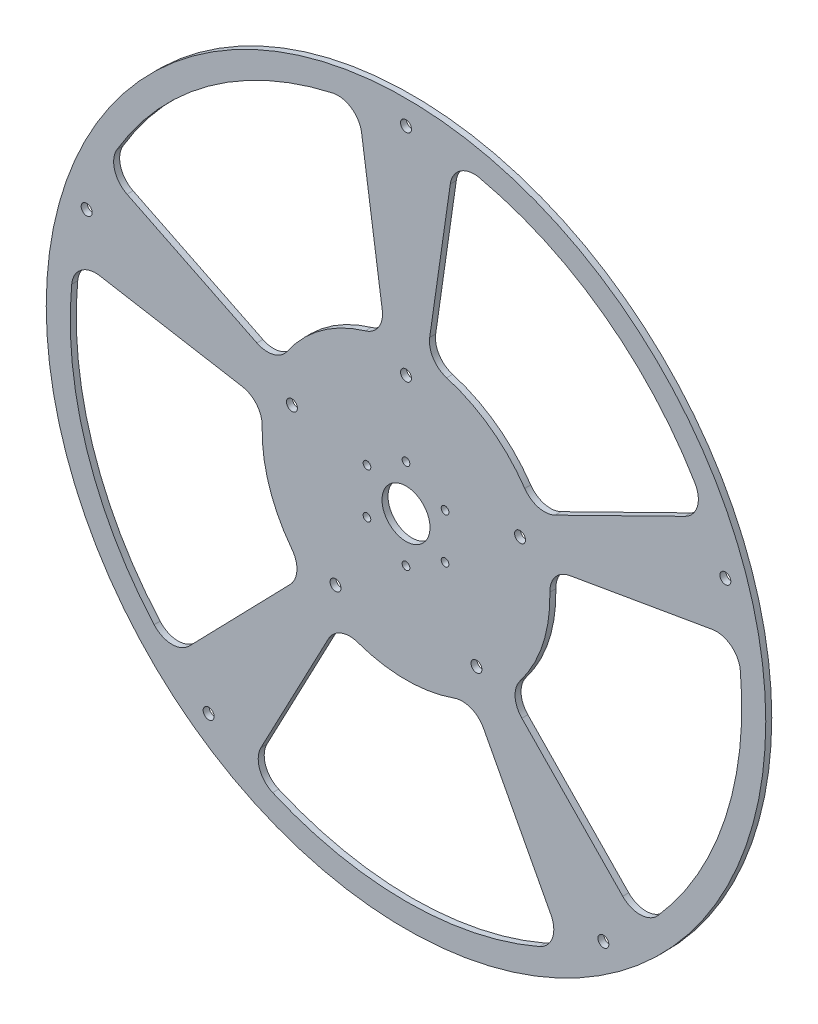
SolidWorks part; units mm, degrees
material "6061 Alloy"
ref_plane "Front Plane" through (0, 0, 0) normal (0, 0, 1) x (1, 0, 0)
ref_plane "Top Plane" through (0, 0, 0) normal (0, 1, 0) x (1, 0, 0)
ref_plane "Right Plane" through (0, 0, 0) normal (1, 0, 0) x (0, 0, -1)
sketch "Sketch1" plane through (0, 0, 0) normal (0, 0, 1) x (1, 0, 0)
  line L0 (0, 177.8) -> (0, 0) construction
  line L1 (0, 0) -> (169.0978, 54.9432) construction
  line L2 (-169.0978, 54.9432) -> (0, 0) construction
  line L3 (0, 0) -> (-104.5082, -143.8432) construction
  line L4 (0, 0) -> (104.5082, -143.8432) construction
  line L5 (25.3351, 175.9857) -> (10.8579, 75.4224)
  line L6 (-25.4, 175.9764) -> (-10.8857, 75.4184)
  line L7 (68.3757, 33.6333) -> (159.5434, 78.4777)
  line L8 (75.0863, 12.9803) -> (175.2013, 30.2874)
  line L9 (53.1164, -54.6359) -> (123.9384, -127.4838)
  line L10 (35.548, -67.4002) -> (82.9453, -157.267)
  line L11 (-159.5434, 78.4777) -> (-68.3757, 33.6333)
  line L12 (-175.2013, 30.2874) -> (-75.0863, 12.9803)
  line L13 (-82.9453, -157.267) -> (-35.548, -67.4002)
  line L14 (-123.9384, -127.4838) -> (-53.1164, -54.6359)
  line L15 (0, 0) -> (-8.0097, 4.6244) construction
  line L16 (-8.0097, 4.6244) -> (-8.0097, -4.6244) construction
  line L17 (-8.0097, -4.6244) -> (0, -9.2488) construction
  line L18 (0, -9.2488) -> (8.0097, -4.6244) construction
  line L19 (8.0097, -4.6244) -> (8.0097, 4.6244) construction
  line L20 (8.0097, 4.6244) -> (0, 9.2488) construction
  line L21 (0, 9.2488) -> (-8.0097, 4.6244) construction
  line L22 (-8.0097, 4.6244) -> (-20.6772, 11.938) construction
  line L23 (0, 0) -> (0, 9.2488) construction
  line L24 (0, 9.2488) -> (0, 23.876) construction
  line L25 (0, 0) -> (8.0097, 4.6244) construction
  line L26 (8.0097, 4.6244) -> (20.6772, 11.938) construction
  line L27 (0, 0) -> (8.0097, -4.6244) construction
  line L28 (8.0097, -4.6244) -> (20.6772, -11.938) construction
  line L29 (0, 0) -> (0, -9.2488) construction
  line L30 (0, -9.2488) -> (0, -23.876) construction
  line L31 (0, 0) -> (-8.0097, -4.6244) construction
  line L32 (-8.0097, -4.6244) -> (-20.6772, -11.938) construction
  circle A0 centre (0, 0) radius 190.5
  arc A1 (-10.8857, 75.4184) -> (-68.3757, 33.6333) centre (0, 0) ccw
  arc A2 (-25.4, 175.9764) -> (-159.5434, 78.4777) centre (0, 0) ccw
  arc A3 (68.3757, 33.6333) -> (10.8579, 75.4224) centre (0, 0) ccw
  arc A4 (-75.0863, 12.9803) -> (-53.1164, -54.6359) centre (0, 0) ccw
  arc A5 (53.1164, -54.6359) -> (75.0863, 12.9803) centre (0, 0) ccw
  arc A6 (-35.548, -67.4002) -> (35.548, -67.4002) centre (0, 0) ccw
  arc A7 (159.5434, 78.4777) -> (25.3351, 175.9857) centre (0, 0) ccw
  arc A8 (123.9384, -127.4838) -> (175.2013, 30.2874) centre (0, 0) ccw
  arc A9 (-82.9453, -157.267) -> (82.9453, -157.267) centre (0, 0) ccw
  arc A10 (-175.2013, 30.2874) -> (-123.9384, -127.4838) centre (0, 0) ccw
  circle A11 centre (0, 0) radius 76.2 construction
  circle A12 centre (0, 0) radius 177.8 construction
  circle A13 centre (0, 0) radius 12.7
  circle A15 centre (-37.3244, -51.3726) radius 2.9
  circle A19 centre (-169.0978, 54.9432) radius 2.9
  circle A20 centre (0, 177.8) radius 2.9
  circle A21 centre (169.0978, 54.9432) radius 2.9
  circle A22 centre (104.5082, -143.8432) radius 2.9
  circle A23 centre (-104.5082, -143.8432) radius 2.9
  circle A24 centre (0, 0) radius 8.0097 construction
  circle A25 centre (-20.6772, 11.938) radius 2.032
  circle A26 centre (0, 23.876) radius 2.032
  circle A27 centre (20.6772, 11.938) radius 2.032
  circle A28 centre (20.6772, -11.938) radius 2.032
  circle A29 centre (0, -23.876) radius 2.032
  circle A30 centre (-20.6772, -11.938) radius 2.032
  circle A31 centre (-60.3921, 19.6226) radius 2.9
  circle A32 centre (0, 63.5) radius 2.9
  circle A33 centre (60.3921, 19.6226) radius 2.9
  circle A34 centre (37.3244, -51.3726) radius 2.9
  point P25 (0, 0)
  point P31 (0, 0)
  point P55 (0, 0)
  point P77 (0, 0)
  point P78 (0, 0)
  dimension "D1" = 381
  dimension "D2" = 152.4
  dimension "D3" = 355.6
  dimension "D22" = 25.4
  dimension "D23" = 5
  dimension "D24" = 74.6487
  dimension "D25" = 5.8
  dimension "D26" = 63.5
  dimension "D33" = 5.8
  dimension "D36" = 4.064
  dimension "D4" = 72
  dimension "D5" = 72
  dimension "D6" = 72
  dimension "D7" = 72
  dimension "D8" = 25.4
  dimension "D9" = 25.4
  dimension "D10" = 25.4
  dimension "D11" = 25.4
  dimension "D12" = 25.4
  dimension "D13" = 25.4
  dimension "D14" = 25.4
  dimension "D15" = 25.4
  dimension "D16" = 25.4
  dimension "D17" = 25.4
  dimension "D18" = 21.7158
  dimension "D19" = 50.6702
  dimension "D20" = 50.6702
  dimension "D21" = 50.7351
  dimension "D30" = 63.5
  dimension "D35" = 23.876
  dimension "D34" = 5
  dimension "D37" = 6
extrude "Boss-Extrude3" add sketch "Sketch1" along normal blind 3.175
fillet "Fillet1" radius 12.7 1 edges at (-175.2013, 30.2874, 1.5875)
fillet "Fillet2" radius 12.7 13 edges at (35.548, -67.4002, 1.5875) (123.9384, -127.4838, 1.5875) (53.1164, -54.6359, 1.5875) (75.0863, 12.9803, 1.5875) (175.2013, 30.2874, 1.5875) (68.3757, 33.6333, 1.5875) (159.5434, 78.4777, 1.5875) (25.3351, 175.9857, 1.5875) (10.8579, 75.4224, 1.5875) (-10.8857, 75.4184, 1.5875) (-68.3757, 33.6333, 1.5875) (-25.4, 175.9764, 1.5875) (-159.5434, 78.4777, 1.5875)
fillet "Fillet3" radius 12.7 6 edges at (-75.0863, 12.9803, 1.5875) (-123.9384, -127.4838, 1.5875) (-53.1164, -54.6359, 1.5875) (82.9453, -157.267, 1.5875) (-82.9453, -157.267, 1.5875) (-35.548, -67.4002, 1.5875)
